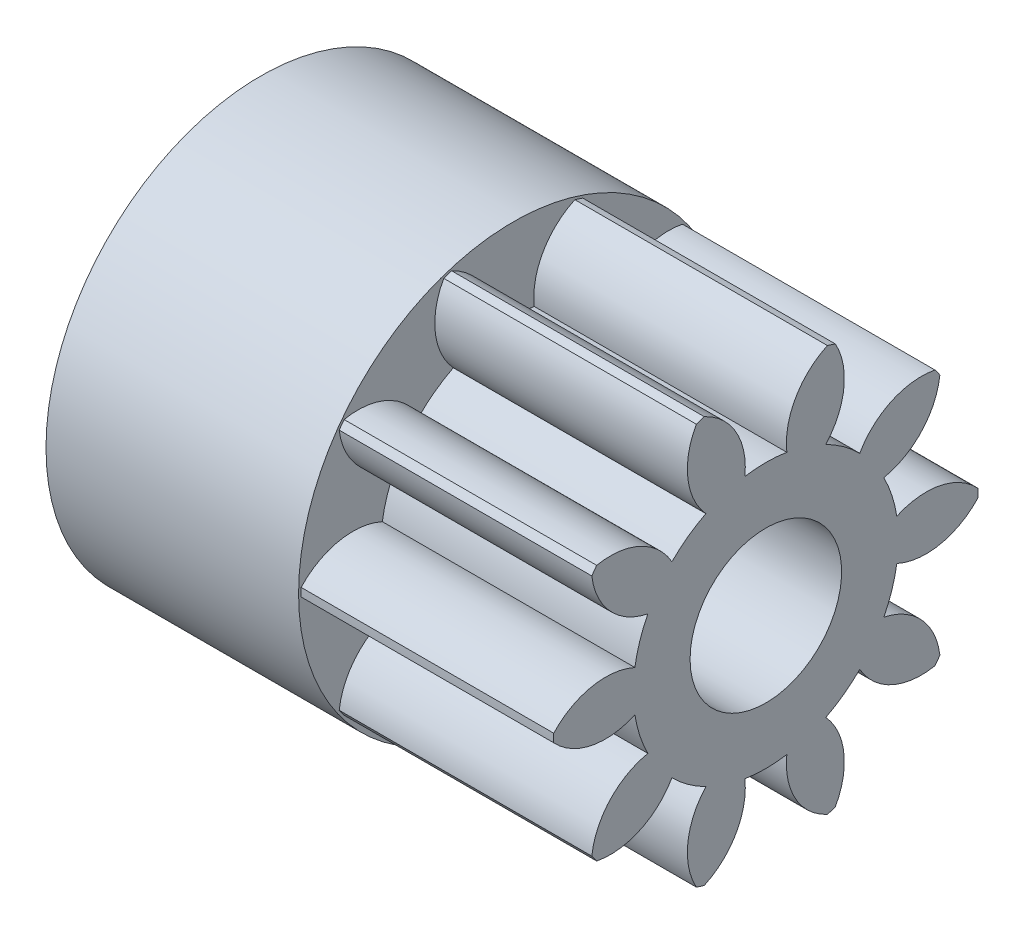
SolidWorks part; units mm, degrees
ref_plane "Plane1" through (0, 0, 0) normal (0, 0, 1) x (1, 0, 0)
ref_plane "Plane2" through (0, 0, 0) normal (0, 1, 0) x (1, 0, 0)
ref_plane "Plane3" through (0, 0, 0) normal (1, 0, 0) x (0, 0, -1)
sketch "HoldingSke" plane through (0, 0, 0) normal (0, 1, 0) x (1, 0, 0)
  line L0 (0, 0) -> (1.4069, -0.2481)
  line L1 (-15, 0) -> (100, 0) construction
  line L2 (0, 0) -> (-2.1039, 2.3779)
  line L3 (0, 0) -> (-11.863, 4.5341)
  line L4 (0, 0) -> (8.5048, 1.4996)
  line L5 (0, 0) -> (-46.8476, -17.4728)
  line L6 (0, 0) -> (-4.1448, -2.7965)
  line L7 (-2.1039, 2.3779) -> (8.6586, 51.2059)
  line L8 (-76.2, 54.61) -> (-75.7, 54.61)
  line L9 (-71.009, 38.7566) -> (-53.1078, 45.2721)
  line L10 (-76.2, 71.12) -> (104.1128, 71.12)
  line L11 (0, 0) -> (-5, 0)
  line L12 (-76.2, 101.6) -> (-76.173, 101.6)
  line L13 (24.9733, 27.94) -> (52.9518, 28.4284)
  line L14 (24.9733, 27.94) -> (24.9743, 27.94)
  line L15 (24.9733, 27.94) -> (100.4006, 29.5858)
  line L16 (-63.627, -0.7) -> (-12.827, -0.7)
  circle A0 centre (0, 0) radius 1.5
  circle A1 centre (0, 0) radius 2.624
  circle A2 centre (0, 0) radius 37.5
  circle A3 centre (0, 0) radius 1.5
  dimension "Num_teeth" = 10
  dimension "Pitch_radius" = 180.3128
  dimension "Width" = 5
  dimension "Thickness" = 5
sketch "BasProSke" plane through (0, 0, 0) normal (0, 1, 0) x (1, 0, 0)
  line L0 (-10, 0) -> (60, 0) construction
  line L1 (0, 0) -> (0, 4.2)
  line L2 (0, 0) -> (5, 0)
  line L3 (5, 0) -> (5, 4.2)
  line L4 (5, 4.2) -> (0, 4.2)
  dimension "Thickness" = 5
  dimension "Diameter" = 8.4
revolve "Base-Revolve" add sketch "BasProSke" angle 360 about L0
sketch "TooCutSke" plane through (0, 0, 0) normal (1, 0, 0) x (0, 0, -1)
  line L1 (0, 0) -> (0, 107) construction
  line L2 (0, 0) -> (-0.5947, 3.4491) construction
  line L3 (0, 0) -> (-2.1409, 6.589) construction
  line L4 (-0.5947, 3.4491) -> (-1.0705, 3.2945) construction
  arc A0 (0.4155, 2.5909) -> (-0.4155, 2.5909) centre (0, 0) ccw
  arc A1 (1.2546, 4.0349) -> (-1.2546, 4.0349) centre (0, 0) ccw
  circle A2 centre (0, 0) radius 3.5 construction
  circle A3 centre (0, 0) radius 3.2889 construction
  arc A4 (-0.4155, 2.5909) -> (-1.2546, 4.0349) centre (-1.8066, 2.7483) ccw
  arc A5 (1.2546, 4.0349) -> (0.4155, 2.5909) centre (1.8066, 2.7483) ccw
extrude "ToothCut" cut sketch "TooCutSke" along normal through all
fillet "Breaks" [suppressed] radius 0.014 tangent propagation no
fillet "RootFillets" [suppressed] radius 0.176
pattern_circular "TeethCuts" count 10 every 36 about axis through (-10, 0, 0) along (1, 0, 0) of "ToothCut", "RootFillets", "Breaks"
sketch "HubNeaOneSke" plane through (0, 0, 0) normal (-1, 0, 0) x (0, 0, 1)
  circle A0 centre (0, 0) radius 2.624
  dimension "Diameter" = 5.248
extrude "HubNearOne" [suppressed] add sketch "HubNeaOneSke" along normal blind 45.0001
sketch "HubNeaBotSke" plane through (0, 0, 0) normal (-1, 0, 0) x (0, 0, 1)
  circle A0 centre (0, 0) radius 2.624
  dimension "Diameter" = 5.248
extrude "HubNearBoth" [suppressed] add sketch "HubNeaBotSke" along normal blind 22.5
ref_plane "FarPln" through (5, 0, 0) normal (1, 0, 0) x (0, 0, -1)
sketch "HubFarSke" plane through (5, 0, 0) normal (1, 0, 0) x (0, 0, -1)
  circle A0 centre (0, 0) radius 2.624
  dimension "Diameter" = 5.248
extrude "HubFar" [suppressed] add sketch "HubFarSke" along normal blind 22.5
sketch "BorSke" plane through (0, 0, 0) normal (1, 0, 0) x (0, 0, -1)
  circle A0 centre (0, 0) radius 1.5
  dimension "Diameter" = 3
extrude "Bore" cut sketch "BorSke" along normal mid plane 100.0001
sketch "KeySke" plane through (0, 0, 0) normal (1, 0, 0) x (0, 0, -1)
  line L0 (-0.6, 0) -> (-0.6, 2)
  line L1 (-0.6, 2) -> (0.6, 2)
  line L2 (0.6, 2) -> (0.6, 0)
  line L3 (0, 0) -> (0, 34) construction
  line L4 (-0.6, 0) -> (0.6, 0)
  dimension "Width" = 1.2
extrude "Keyway" [suppressed] cut sketch "KeySke" along normal mid plane 100.0001
pattern_circular "Keyway2" [suppressed] count 2 every 90 about axis through (-10, 0, 0) along (1, 0, 0) reverse direction yes
sketch "Croquis1" plane through (0, 0, 0) normal (-1, 0, 0) x (0, 0, 1)
  circle A0 centre (0, 0) radius 4.25
  circle A1 centre (0, 0) radius 3.25
  dimension "D1" = 8.5
  dimension "D2" = 6.5
extrude "Saliente-Extruir1" add sketch "Croquis1" along normal blind 5
sketch "Croquis2" plane through (0, 0, 0) normal (-1, 0, 0) x (0, 0, 1)
  circle A0 centre (0, 0) radius 3.25
  circle A1 centre (0, 0) radius 3.25 construction
extrude "Saliente-Extruir2" add sketch "Croquis2" along normal blind 2
sketch "Croquis3" plane through (-2, 0, 0) normal (-1, 0, 0) x (0, 0, 1)
  line L0 (-1.95, 2.6) -> (-1.95, -2.6)
  circle A0 centre (0, 0) radius 3.25 construction
  circle A1 centre (0, 0) radius 3.25 construction
  arc A2 (-1.95, 2.6) -> (-1.95, -2.6) centre (0, 0) ccw
  dimension "D1" = 5.2
extrude "Saliente-Extruir3" add sketch "Croquis3" along normal blind 2
equation "' \"Module@HoldingSke\" = 6.35"
equation "' \"Num_teeth@HoldingSke\" = 12"
equation "' \"Ap@HoldingSke\" =  20"
equation "' \"Ap@HoldingSke\" = 20"
equation "' \"Width@HoldingSke\" = 0.5 * 25.4"
equation "' \"Hub_dia@HoldingSke\"= 1 * 25.4"
equation "' \"Hub_dia@HoldingSke\" = 1 * 25.4"
equation "' \"Overall_len@HoldingSke\" = 1.0 * 25.4"
equation "' \"Bore@HoldingSke\" = 0.75 * 25.4"
equation "' \"T_dim@HoldingSke\" = 0.1 * 25.4"
equation "' \"Width@KeySke\" = 0.25 * 25.4"
equation "' \"Show_teeth@HoldingSke\" = 13"
equation "' \"Backlash@HoldingSke\" = 0.009 * 25.4"
equation "' \"Addendum_fac@HoldingSke\" = 1.0"
equation "' \"Dedendum_fac@HoldingSke\" = 1.25"
equation "' \"Dedendum_add@HoldingSke\" = 0.00005 * 25.4"
equation "' \"Clearance_fac@HoldingSke\" = 0.25"
equation "\"Pitch@HoldingSke\" = 1 / \"Module@HoldingSke\""
equation "\"Overcut_dia@TooCutSke\" = (\"Num_teeth@HoldingSke\" + 2 * \"Addendum_fac@HoldingSke\") / \"Pitch@HoldingSke\" + 0.002 * 25.4"
equation "\"Pitch_dia@TooCutSke\" = \"Num_teeth@HoldingSke\" / \"Pitch@HoldingSke\""
equation "\"Base_dia@TooCutSke\" = \"Num_teeth@HoldingSke\" / \"Pitch@HoldingSke\" * cos((\"Ap@HoldingSke\"  * 3.14159265 / 180))"
equation "\"Root_dia@TooCutSke\" = (\"Num_teeth@HoldingSke\" + 2) / \"Pitch@HoldingSke\" - 2 * (\"Addendum_fac@HoldingSke\" + \"Dedendum_fac@HoldingSke\") / \"Pitch@HoldingSke\" - \"Dedendum_add@HoldingSke\" * 2"
equation "\"Half_ang@TooCutSke\" = 180 / \"Num_teeth@HoldingSke\""
equation "\"Half_CT@TooCutSke\" = \"Num_teeth@HoldingSke\" / \"Pitch@HoldingSke\" * sin((3.14159265 / 2 / \"Num_teeth@HoldingSke\")) / 2 - 7 * \"Backlash@HoldingSke\" / 4"
equation "\"Flank_rad@TooCutSke\" = \"Num_teeth@HoldingSke\" / \"Pitch@HoldingSke\" / 5"
equation "\"Radius@RootFillets\" = \"Clearance_fac@HoldingSke\" / \"Pitch@HoldingSke\" + \"Dedendum_add@HoldingSke\""
equation "\"Break_rad@Breaks\" = 0.02 / \"Pitch@HoldingSke\""
equation "\"Thickness@HoldingSke\" = \"Width@HoldingSke\""
equation "\"OAL@HoldingSke\" = \"Thickness@HoldingSke\""
equation "\"MHD@HoldingSke\" = (\"Num_teeth@HoldingSke\" + 2) / \"Pitch@HoldingSke\" - 2 * (\"Addendum_fac@HoldingSke\" + \"Dedendum_fac@HoldingSke\")  / \"Pitch@HoldingSke\" - \"Dedendum_add@HoldingSke\" * 2"
equation "\"MBD@HoldingSke\" = (\"Num_teeth@HoldingSke\" + 2) / \"Pitch@HoldingSke\" - 2 * (\"Addendum_fac@HoldingSke\" + \"Dedendum_fac@HoldingSke\")  / \"Pitch@HoldingSke\" - \"Dedendum_add@HoldingSke\" * 2 - 0.002 * 25.4"
equation "\"MHD@HoldingSke\" = ((sgn( \"MHD@HoldingSke\" - \"Hub_dia@HoldingSke\" )-1)*( \"MHD@HoldingSke\" - \"Hub_dia@HoldingSke\" ))/-2+ \"Hub_dia@HoldingSke\""
equation "\"MBD@HoldingSke\" = ((sgn( \"MBD@HoldingSke\" - \"Bore@HoldingSke\" )-1)*( \"MBD@HoldingSke\" - \"Bore@HoldingSke\" ))/-2+ \"Bore@HoldingSke\""
equation "\"OAL@HoldingSke\" = ((sgn( \"OAL@HoldingSke\" - \"Overall_len@HoldingSke\" )+1)*( \"OAL@HoldingSke\" - \"Overall_len@HoldingSke\" ))/2 + \"Overall_len@HoldingSke\" + 0.000002 * 25.4"
equation "\"Num_teeth@TeethCuts\" = int( \"Show_teeth@HoldingSke\" ) + 1"
equation "\"Num_teeth@TeethCuts\" = ((sgn( \"Num_teeth@TeethCuts\" - \"Num_teeth@HoldingSke\" )-1)*( \"Num_teeth@TeethCuts\" - \"Num_teeth@HoldingSke\" ))/-2+ \"Num_teeth@HoldingSke\""
equation "\"Num_teeth@TeethCuts\" = ((sgn( \"Num_teeth@TeethCuts\" - 2.0)+1)*( \"Num_teeth@TeethCuts\" - 2.0))/2 +2.0"
equation "\"Angle@TeethCuts\" = 360.0 / \"Num_teeth@HoldingSke\""
equation "\"Diameter@BasProSke\" = (\"Num_teeth@HoldingSke\" + 2 * \"Addendum_fac@HoldingSke\") / \"Pitch@HoldingSke\""
equation "\"Thickness@BasProSke\"  = \"Thickness@HoldingSke\""
equation "' \"Fillet_rad@BasProSke\" =  \"Thickness@HoldingSke\" * 0.05"
equation "' \"Fillet_rad@BasProSke\" = \"Thickness@HoldingSke\" * 0.05"
equation "\"MHD@HoldingSke\" = ((sgn( \"MHD@HoldingSke\" - \"Root_dia@TooCutSke\" )-1)*( \"MHD@HoldingSke\" - \"Root_dia@TooCutSke\" ))/-2+ \"Root_dia@TooCutSke\""
equation "\"Diameter@HubNeaOneSke\" = \"MHD@HoldingSke\""
equation "\"Length@HubNearOne\" = \"OAL@HoldingSke\" - \"Thickness@BasProSke\""
equation "\"Diameter@HubNeaBotSke\" = \"MHD@HoldingSke\""
equation "\"Length@HubNearBoth\" = ( \"OAL@HoldingSke\" - \"Thickness@BasProSke\" ) / 2.0"
equation "\"Thickness@FarPln\" = \"Thickness@BasProSke\""
equation "\"Diameter@HubFarSke\" = \"MHD@HoldingSke\""
equation "\"Length@HubFar\" = ( \"OAL@HoldingSke\" - \"Thickness@BasProSke\" ) / 2.0"
equation "\"Diameter@BorSke\" = \"MBD@HoldingSke\""
equation "\"D1@Bore\" = \"OAL@HoldingSke\" * 2.0"
equation "\"D1@Keyway\" = \"OAL@HoldingSke\" * 2.0"
equation "\"Offset@KeySke\" = \"T_dim@HoldingSke\" + \"MBD@HoldingSke\" / 2.0"
